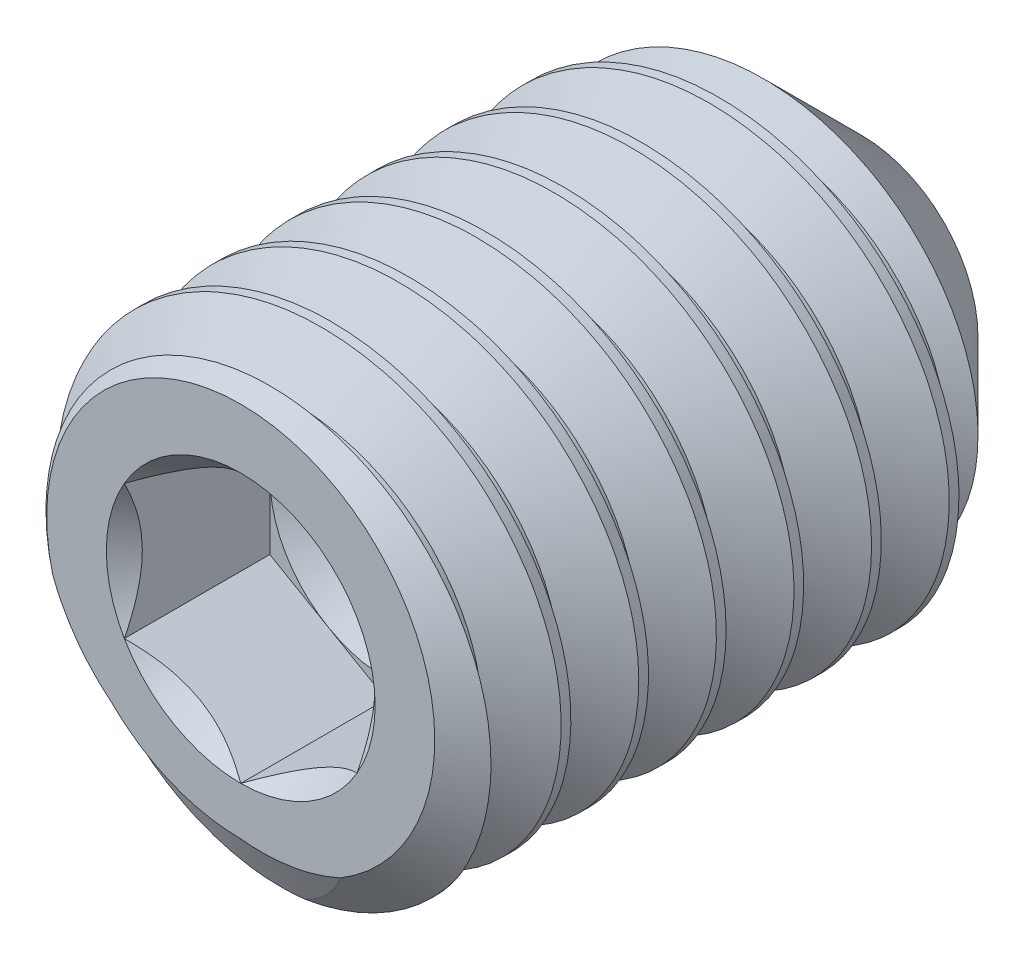
SolidWorks part; units mm, degrees
other "Imported1" parameters "D3"=8.8, "D1"=46.842, "Length"=8, "Drive Size"=3, "Thread Size"=6, "Thread Pitch"=1, "D2"=0.0866, "hex Depth"=1.875, "Dia"=12, "D4"=2.3829, "Cup Point Dia"=3.3528, "D5"=1.436, "D6"=1.4986, "D7"=5.0014, "Pitch"=1.75
ref_plane "Front" through (0, 0, 0) normal (0, 0, 1) x (1, 0, 0)
ref_plane "Top" through (0, 0, 0) normal (0, 1, 0) x (1, 0, 0)
ref_plane "Right" through (0, 0, 0) normal (1, 0, 0) x (0, 0, -1)
sketch "Sketch1" plane through (0, 0, 0) normal (1, 0, 0) x (0, 0, -1)
  line L0 (4, 3) -> (-4, 3) construction
  line L1 (-4, 3) -> (-4, -3) construction
  line L2 (-4, -3) -> (4, -3) construction
  line L3 (4, -3) -> (4, 3) construction
  line L4 (-4, 1.5) -> (-4, -1.5) construction
  line L5 (3.9375, 3.1083) -> (4.9375, 3.1083) construction
  line L6 (3.9375, 3.1083) -> (4, 3) construction
  line L7 (4, 3) -> (4.875, 3) construction
  line L8 (4.875, 3) -> (4.9375, 3.1083) construction
  line L9 (4, 3) -> (4.4375, 2.2422) construction
  line L10 (4.4375, 2.2422) -> (4.875, 3) construction
  line L11 (4.375, 2.3505) -> (4.5, 2.3505) construction
  line L12 (4.4375, 3.1083) -> (4.4375, 3) construction
  line L13 (4.4375, 2.3505) -> (4.4375, 2.2422) construction
  point P3 (0, 3)
  point P24 (-4, 0)
  point P25 (-4, 0)
  dimension "D1" = 0.125
sketch "Sketch11" plane through (0, 0, 0) normal (1, 0, 0) x (0, 0, -1)
  line L0 (-4, 0) -> (-4, 2.5)
  line L1 (-4, 2.5) -> (-3.6499, 3)
  line L2 (-3.6499, 3) -> (2.5, 3)
  line L3 (2.5, 3) -> (4, 1.5)
  line L4 (4, 1.5) -> (3.0987, 0)
  line L5 (3.0987, 0) -> (-4, 0)
  line L6 (3.0987, 0) -> (4, 0) construction
  line L7 (4, 0) -> (4, 1.5) construction
  line L8 (4, -1.5) -> (3.0987, 0) construction
  line L9 (-3.6499, -3) -> (2.5, -3) construction
  line L10 (-4, -3) -> (4, -3) construction
  line L11 (-4, 3) -> (-4, -3) construction
  line L12 (4, -3) -> (4, 3) construction
  point P11 (0.5, -3)
  point P12 (-4, 3)
  dimension "D3" = 35
  dimension "D5" = 118
  dimension "D6" = 45
  dimension "D1" = 0.5
  dimension "D2" = 3.5
  dimension "D4" = 1.5
revolve "Revolve1" add sketch "Sketch11" angle 360 about L6
sketch "Sketch2" plane through (0, 0, 4) normal (0, 0, 1) x (1, 0, 0)
  line L1 (0, 1.7321) -> (-1.5, 0.866)
  line L2 (-1.5, 0.866) -> (-1.5, -0.866)
  line L3 (-1.5, -0.866) -> (0, -1.7321)
  line L4 (0, -1.7321) -> (1.5, -0.866)
  line L5 (1.5, -0.866) -> (1.5, 0.866)
  line L6 (1.5, 0.866) -> (0, 1.7321)
  circle A0 centre (0, 0) radius 1.5 construction
  circle A1 centre (0, 0) radius 3 construction
extrude "Cut-Extrude1" cut sketch "Sketch2" against normal blind 1.875
sketch "Sketch3" plane through (0, 0, 4) normal (0, 0, 1) x (1, 0, 0)
  circle A0 centre (0, 0) radius 1.7321
extrude "Cut-Extrude2" cut sketch "Sketch3" against normal through all draft 45
sketch "Sketch4" plane through (0, 0, 2.125) normal (0, 0, 1) x (1, 0, 0)
  circle A0 centre (0, 0) radius 1.5 construction
  circle A1 centre (0, 0) radius 1.5
extrude "Cut-Extrude3" cut sketch "Sketch4" against normal through all draft 60
sketch "Sketch13" plane through (0, 0, 0) normal (1, 0, 0) x (0, 0, -1)
  line L0 (0, -3) -> (0, 3) construction
  line L2 (-3.6499, 3) -> (2.5, 3) construction
  line L4 (3.0987, 0) -> (-4, 0) construction
  point P0 (-2.9013, 0)
  point P4 (0, 0)
  point P9 (2.9013, 0)
  dimension "D1" = 6
ref_plane "Plane1" through (0, 0, -4) normal (0, 0, 1) x (1, 0, 0)
sketch "Sketch5" plane through (0, 0, -4) normal (0, 0, 1) x (1, 0, 0)
  circle A0 centre (0, 0) radius 3 construction
  circle A1 centre (0, 0) radius 3
curve "Helix/Spiral1" pitch 1 height 8.8 radius 3 centre (0, 0, -4) axis (0, 0, 1) start towards (0, 1, 0)
sketch "Sketch6" plane through (0, 0, 0) normal (1, 0, 0) x (0, 0, -1)
  line L0 (3.9688, 3.0541) -> (4.9063, 3.0541)
  line L1 (3.9375, 3.1083) -> (4, 3) construction
  line L2 (4.875, 3) -> (4.9375, 3.1083) construction
  line L3 (4.9063, 3.0541) -> (4.5, 2.3505)
  line L4 (4.5, 2.3505) -> (4.375, 2.3505)
  line L5 (4.375, 2.3505) -> (3.9688, 3.0541)
sweep "Cut-Sweep1" cut profiles "Sketch6" path "Helix/Spiral1"
equation "\"D3@Helix/Spiral1\" = \"Length@Sketch1\" * 1.1"
equation "\"hex Depth@Cut-Extrude1\"=\"Drive Size@Sketch1\" * .625"
equation "\"D1@Sketch11\" = \"Thread Pitch@Sketch1\" * .5"
equation "\"D2@Sketch11\" = \"Thread Pitch@Sketch1\" * 3.5"
equation "\"D1@Helix/Spiral1\" = \"Thread Pitch@Sketch1\""
equation "\"D4@Sketch11\" = \"Thread Pitch@Sketch1\" * 1.5"
equation "\"D1@Sketch1\" = \"Thread Pitch@Sketch1\" / 8"
equation "\"D1@Sketch13\"=\"Thread Size@Sketch1\""
